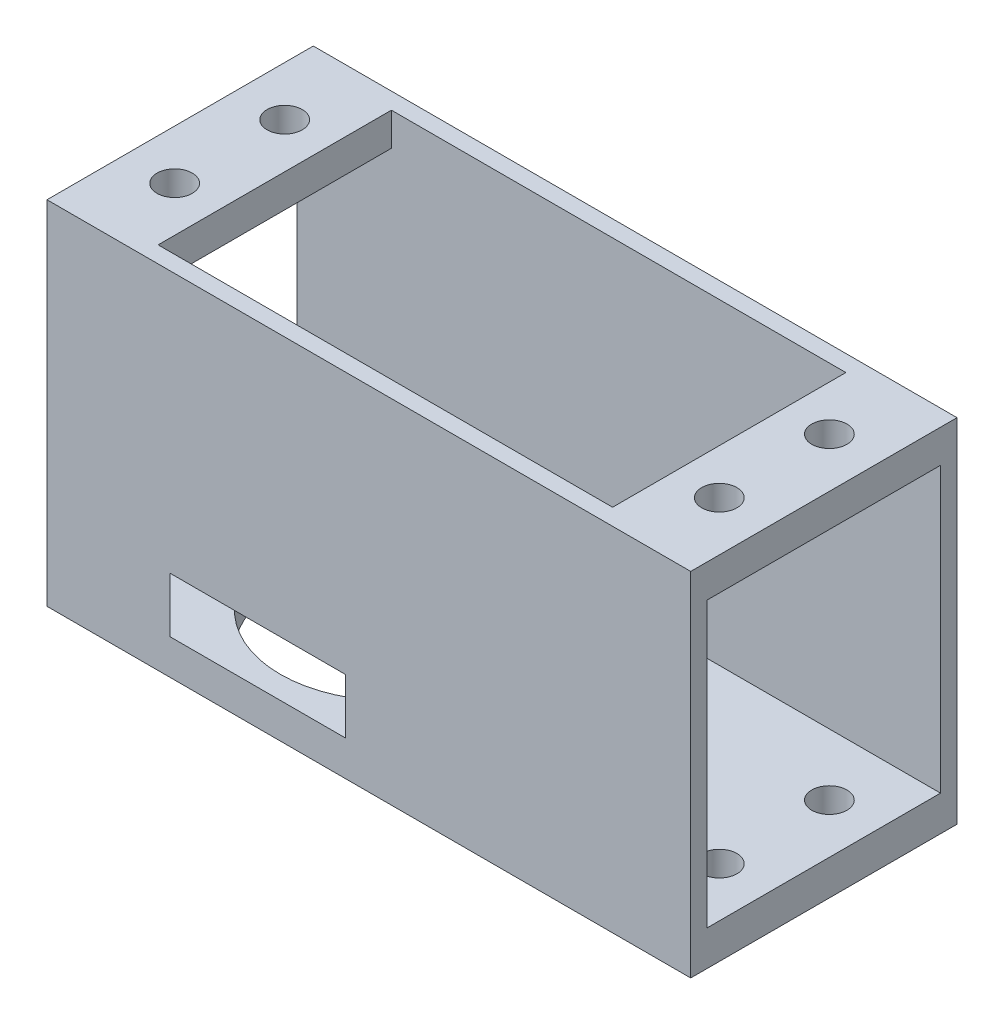
SolidWorks part; units mm, degrees
ref_plane "Front Plane" through (0, 0, 0) normal (0, 0, 1) x (1, 0, 0)
ref_plane "Top Plane" through (0, 0, 0) normal (0, 1, 0) x (1, 0, 0)
ref_plane "Right Plane" through (0, 0, 0) normal (1, 0, 0) x (0, 0, -1)
sketch "Channel Sketch" plane through (0, 0, 0) normal (1, 0, 0) x (0, 0, -1)
  line L0 (-12.1, 12.2) -> (12.1, 12.2)
  line L1 (12.1, 12.2) -> (12.1, 44.2)
  line L2 (12.1, 44.2) -> (10.6, 44.2)
  line L3 (10.6, 44.2) -> (10.6, 15.4)
  line L4 (10.6, 15.4) -> (-10.6, 15.4)
  line L5 (-10.6, 15.4) -> (-10.6, 44.2)
  line L6 (-10.6, 44.2) -> (-12.1, 44.2)
  line L7 (-12.1, 44.2) -> (-12.1, 12.2)
extrude "Channel" add sketch "Channel Sketch" along normal blind 39.35 and the other way blind 19.15
ref_axis "Stem Axis" through (0, 10.6, 0) along (0, 1, 0)
sketch "Flanges Sketch" plane through (0, 0, 0) normal (0, 0, 1) x (1, 0, 0)
  line L0 (-19.15, 41.2) -> (-10.55, 41.2)
  line L1 (-10.55, 41.2) -> (-10.55, 44.2)
  line L2 (-10.55, 44.2) -> (-19.15, 44.2)
  line L3 (-19.15, 44.2) -> (-19.15, 41.2)
  line L4 (30.75, 41.2) -> (39.35, 41.2)
  line L5 (39.35, 41.2) -> (39.35, 44.2)
  line L6 (39.35, 44.2) -> (30.75, 44.2)
  line L7 (30.75, 44.2) -> (30.75, 41.2)
extrude "Flanges" add sketch "Flanges Sketch" along normal mid plane 21.2
sketch "Servo Holes Sketch" plane through (0, 0, 0) normal (0, 1, 0) x (1, 0, 0)
  circle A0 centre (-14.65, -5) radius 1.6
  circle A1 centre (-14.65, 5) radius 1.6
  circle A2 centre (34.85, -5) radius 1.6
  circle A3 centre (34.85, 5) radius 1.6
extrude "Servo Holes" cut sketch "Servo Holes Sketch" against normal mid plane 108.4
sketch "Panel Hole Sketch" plane through (0, 0, 0) normal (0, 1, 0) x (1, 0, 0)
  circle A0 centre (0, 0) radius 10.05
extrude "Panel Hole" cut sketch "Panel Hole Sketch" against normal mid plane 32.8
sketch "Panel Nut Relief Sketch" plane through (0, 0, 0) normal (0, 0, 1) x (1, 0, 0)
  line L0 (0, -500) -> (0, 500) construction
  line L1 (0, 15.4) -> (14.5, 15.4)
  line L2 (14.5, 15.4) -> (14.5, 20.4)
  line L3 (14.5, 20.4) -> (0, 20.4)
  line L4 (0, 20.4) -> (0, 15.4)
revolve "Panel Nut Relief" cut sketch "Panel Nut Relief Sketch" angle 360 about L0
